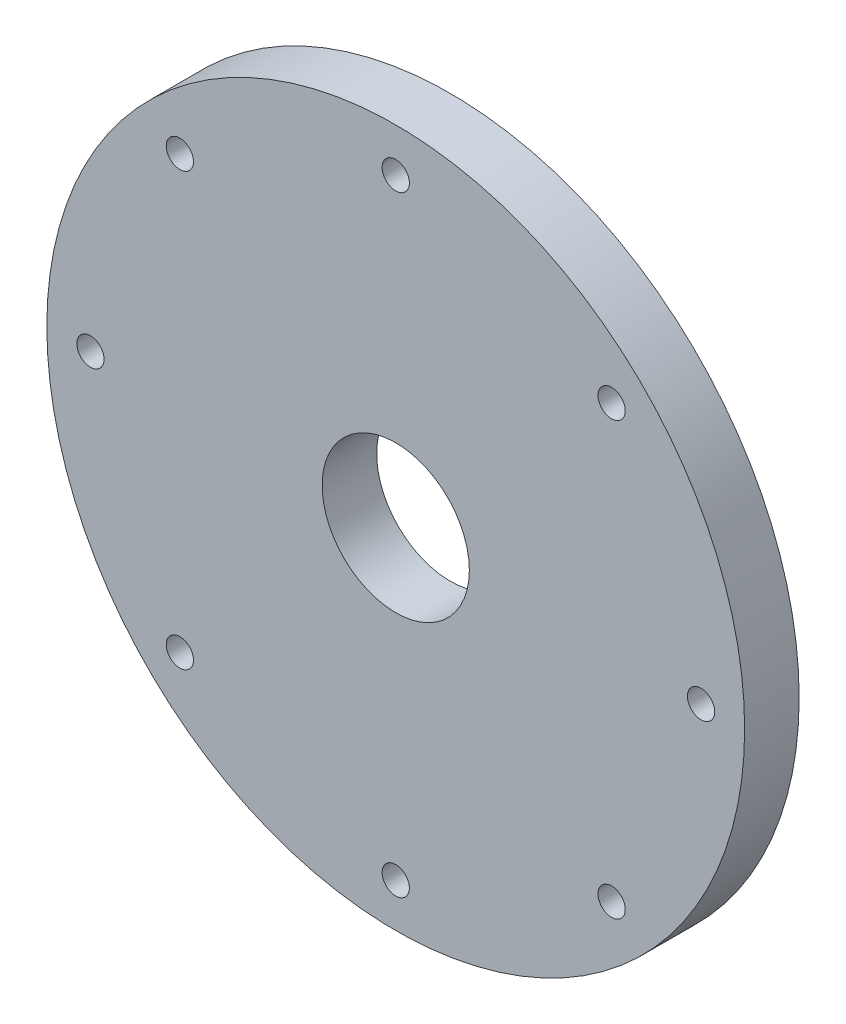
SolidWorks part; units mm, degrees
ref_plane "Alzado" through (0, 0, 0) normal (0, 0, 1) x (1, 0, 0)
ref_plane "Planta" through (0, 0, 0) normal (0, 1, 0) x (1, 0, 0)
ref_plane "Vista lateral" through (0, 0, 0) normal (1, 0, 0) x (0, 0, -1)
sketch "Croquis1" plane through (0, 0, 0) normal (0, 0, 1) x (1, 0, 0)
  circle A0 centre (0, 0) radius 32
  dimension "D1" = 64
extrude "Saliente-Extruir1" add sketch "Croquis1" along normal blind 5
sketch "Croquis2" plane through (0, 0, 5) normal (0, 0, 1) x (1, 0, 0)
  line L0 (0, 0) -> (0, 28) construction
  line L1 (0, 0) -> (19.799, 19.799) construction
  line L2 (0, 0) -> (28, 0) construction
  line L3 (0, 0) -> (19.799, -19.799) construction
  line L4 (0, 0) -> (0, -28) construction
  line L5 (0, 0) -> (-19.799, -19.799) construction
  line L6 (0, 0) -> (-28, 0) construction
  line L7 (0, 0) -> (-19.799, 19.799) construction
  circle A0 centre (0, 28) radius 1.25
  circle A1 centre (0, 0) radius 32 construction
  circle A2 centre (19.799, 19.799) radius 1.25
  circle A3 centre (28, 0) radius 1.25
  circle A4 centre (19.799, -19.799) radius 1.25
  circle A5 centre (0, -28) radius 1.25
  circle A6 centre (-19.799, -19.799) radius 1.25
  circle A7 centre (-28, 0) radius 1.25
  circle A8 centre (-19.799, 19.799) radius 1.25
  point P19 (0, 0)
  dimension "D1" = 2.5
  dimension "D2" = 28
  dimension "D3" = 8
extrude "Cortar-Extruir1" cut sketch "Croquis2" against normal through all
sketch "Croquis3" plane through (0, 0, 5) normal (0, 0, 1) x (1, 0, 0)
  circle A0 centre (0, 0) radius 6.75
  dimension "D1" = 13.5
extrude "Cortar-Extruir2" cut sketch "Croquis3" against normal blind 10
